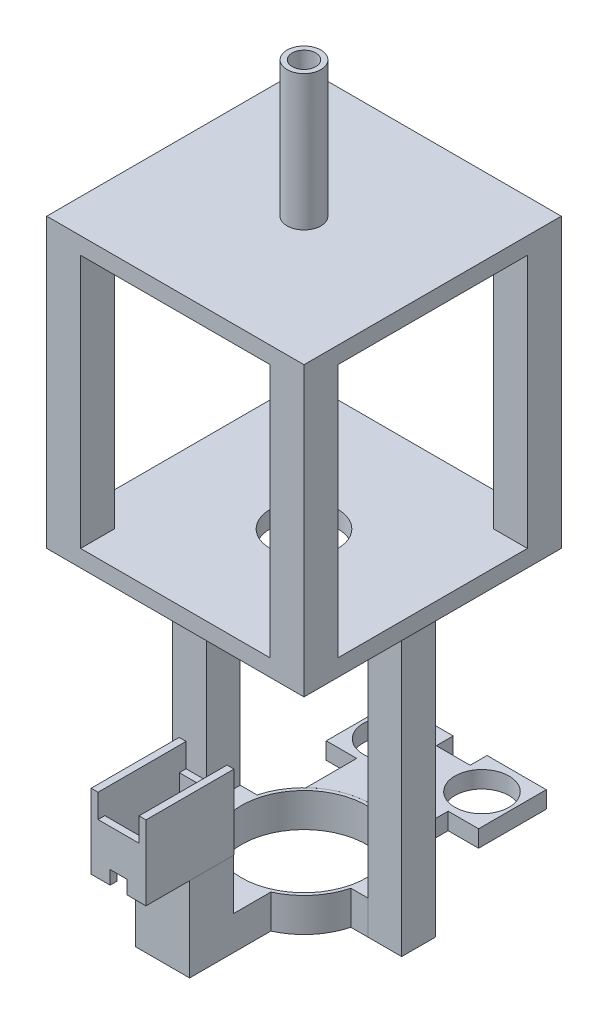
SolidWorks part; units mm, degrees
ref_plane "Front Plane" through (0, 0, 0) normal (0, 0, 1) x (1, 0, 0)
ref_plane "Top Plane" through (0, 0, 0) normal (0, 1, 0) x (1, 0, 0)
ref_plane "Right Plane" through (0, 0, 0) normal (1, 0, 0) x (0, 0, -1)
sketch "Sketch2" plane through (0, 0, 0) normal (0, 1, 0) x (1, 0, 0)
  line L0 (0, 18.5) -> (0, -18.5) construction
  line L1 (-18.5, 0) -> (18.5, 0) construction
  line L2 (0, -5) -> (0, 5) construction
  line L3 (-18.8481, 5) -> (-33.8481, 5)
  line L4 (-33.8481, 5) -> (-33.8481, -5)
  line L5 (-33.8481, -5) -> (-18.8481, -5)
  line L6 (33.8481, -5) -> (18.8481, -5)
  line L7 (33.8481, 5) -> (33.8481, -5)
  line L8 (18.8481, 5) -> (33.8481, 5)
  line L9 (0, 29.0712) -> (22.5, 29.0712)
  line L10 (22.5, 29.0712) -> (22.5, 49.0712)
  line L11 (22.5, 49.0712) -> (5, 49.0712)
  line L12 (-22.5, 49.0712) -> (-22.5, 29.0712)
  line L13 (-22.5, 29.0712) -> (0, 29.0712)
  line L14 (22.5, 39.0712) -> (21.5, 39.0712) construction
  line L20 (-5, 49.0712) -> (-22.5, 49.0712)
  line L21 (0, 44.0712) -> (0, 29.0712) construction
  line L22 (-5, 49.0712) -> (-5, 44.0712)
  line L23 (-5, 44.0712) -> (5, 44.0712)
  line L24 (5, 44.0712) -> (5, 49.0712)
  line L25 (13.5, 47.0712) -> (13.5, 49.0712) construction
  line L26 (13.5, 31.0712) -> (13.5, 29.0712) construction
  line L27 (-13.5, 39.0712) -> (13.5, 39.0712) construction
  line L28 (-13.5, 14.0712) -> (-13.5, 29.0712)
  line L29 (13.5, 29.0712) -> (13.5, 14.0712)
  line L30 (-8, -19.5) -> (8, -19.5) construction
  line L31 (-8, -17.7834) -> (-8, -41.7834)
  line L32 (-8, -41.7834) -> (8, -41.7834)
  line L33 (8, -41.7834) -> (8, -17.7834)
  line L34 (-18.8481, 5) -> (-23.8481, 5) construction
  line L35 (-5.5, -19.5) -> (5.5, -19.5) construction
  line L36 (-23.8481, 5) -> (-23.8481, -5)
  line L37 (23.8481, 5) -> (23.8481, -5)
  circle A0 centre (0, 0) radius 18.5
  circle A1 centre (0, 0) radius 19.5
  circle A2 centre (13.5, 39.0712) radius 8
  circle A3 centre (-13.5, 39.0712) radius 8
  point P9 (0, 0)
  point P45 (0, -19.5)
  point P54 (0, -19.5)
  dimension "D1" = 37
  dimension "D2" = 5
  dimension "D4" = 39
  dimension "D8" = 1
  dimension "D9" = 16
  dimension "D3" = 10
  dimension "D5" = 5
  dimension "D6" = 20
  dimension "D7" = 45
  dimension "D10" = 17.5
  dimension "D11" = 15
  dimension "D12" = 27
  dimension "D13" = 15
  dimension "D14" = 16
  dimension "D15" = 24
  dimension "D16" = 5
extrude "Connector sleeve" add sketch "Sketch2" along normal blind 5 and the other way blind 5 contours A1 A0 | A1 A0 | A1 A0 | A1 A0 region at (-16.3228, 0, -9.6234)
ref_plane "Plane2" through (0, 30, 0) normal (0, 1, 0) x (1, 0, 0)
extrude "Sensor holder" add sketch "Sketch2<10>" along normal blind 5 separate body contours L24 L23 L22 L20 L12 L13 L9 L10 L11 A2 A3 | A1 L29 L9 L13 L28 region at (0, 0, -23.3278) region at (0, 0, -38.234)
sketch "Sketch2<10>" plane through (0, 0, 0) normal (0, 1, 0) x (1, 0, 0) same geometry as "Sketch2"
extrude "Arms" add sketch "Sketch2<18>" along normal blind 85 from offset 5 contours L36 L3 L4 L5 | L8 L37 L6 L7 region at (-28.8481, 0, 0) region at (28.8481, 0, 0) offset against normal yes
sketch "Sketch2<18>" plane through (0, 0, 0) normal (0, 1, 0) x (1, 0, 0) same geometry as "Sketch2"
extrude "Arms2" add sketch "Sketch2<22>" along normal blind 10 from offset 5 contours A1 L3 L4 L5 | A1 L6 L7 L8 | A1 L3 L36 L5 | A1 L6 L37 L8 region at (-21.562, 0, 0) region at (-28.8481, 0, 0) region at (21.562, 0, 0) region at (28.8481, 0, 0) offset against normal yes
sketch "Sketch2<22>" plane through (0, 0, 0) normal (0, 1, 0) x (1, 0, 0) same geometry as "Sketch2"
extrude "Servoholder" add sketch "Sketch2<21>" along normal blind 10 from offset 5 contours A1 L31 L32 L33 region at (0, 0, 30.3552) offset against normal yes
sketch "Sketch2<21>" plane through (0, 0, 0) normal (0, 1, 0) x (1, 0, 0) same geometry as "Sketch2"
sketch "Sketch31" plane through (0, 5, 0) normal (0, 1, 0) x (1, 0, 0)
  line L0 (-8, -41.7834) -> (-8, -28.7834)
  line L1 (-8, -17.7834) -> (-8, -41.7834) construction
  line L2 (-8, -28.7834) -> (8, -28.7834)
  line L3 (8, -41.7834) -> (8, -17.7834) construction
  line L4 (8, -28.7834) -> (8, -41.7834)
  line L5 (8, -41.7834) -> (-8, -41.7834)
  dimension "D1" = 13
extrude "Servoholder2" add sketch "Sketch31" along normal blind 15
sketch "Sketch33" plane through (0, 20, 0) normal (0, 1, 0) x (1, 0, 0)
  line L0 (0, -28.7834) -> (0, -30.7834) construction
  line L1 (8, -28.7834) -> (-8, -28.7834) construction
  line L2 (-8, -41.7834) -> (8, -41.7834) construction
  line L4 (8, -28.7834) -> (-8, -28.7834) construction
  line L6 (-8.1, -28.7834) -> (-8.1, -54.7834)
  line L7 (-8.1, -54.7834) -> (8.1, -54.7834)
  line L8 (8.1, -54.7834) -> (8.1, -28.7834)
  line L9 (0, -41.7834) -> (6.05, -41.7834) construction
  line L10 (0, -54.7834) -> (0, -52.7834) construction
  line L11 (-6.05, -52.7834) -> (6.05, -52.7834)
  line L12 (6.05, -52.7834) -> (6.05, -30.7834)
  line L13 (6.05, -30.7834) -> (-6.05, -30.7834)
  line L14 (-6.05, -52.7834) -> (-6.05, -30.7834)
  line L15 (-8.1, -28.7834) -> (8.1, -28.7834)
  dimension "D1" = 8.1
  dimension "D2" = 26
  dimension "D3" = 6.05
  dimension "D4" = 2
  dimension "D5" = 2
extrude "Servoholder3" add sketch "Sketch33" along normal blind 22
sketch "Servoholder4" plane through (0, 42, 0) normal (0, 1, 0) x (1, 0, 0)
  line L0 (-6.05, -30.7834) -> (-6.05, -28.7834)
  line L1 (8, -28.7834) -> (-8, -28.7834) construction
  line L2 (-6.05, -28.7834) -> (6.05, -28.7834)
  line L3 (8.1, -28.7834) -> (-8.1, -28.7834) construction
  line L4 (6.05, -28.7834) -> (6.05, -30.7834)
  line L5 (6.05, -30.7834) -> (-6.05, -30.7834)
  line L6 (-6.05, -41.7834) -> (6.05, -41.7834) construction
  line L7 (-6.05, -30.7834) -> (-6.05, -52.7834) construction
  line L8 (6.05, -52.7834) -> (6.05, -30.7834) construction
  line L9 (6.05, -54.7834) -> (6.05, -52.7834)
  line L10 (-6.05, -52.7834) -> (-6.05, -54.7834)
  line L11 (-6.05, -54.7834) -> (6.05, -54.7834)
  line L12 (6.05, -52.7834) -> (-6.05, -52.7834)
extrude "Servogrooves" cut sketch "Servoholder4" against normal blind 7
sketch "Sketch36" plane through (0, 0, 54.7834) normal (0, 0, 1) x (1, 0, 0)
  line L0 (0, 20) -> (0, 24) construction
  line L1 (-8.1, 20) -> (8.1, 20) construction
  line L2 (-2.5, 24) -> (2.5, 24)
  line L3 (-2.5, 24) -> (-2.5, 20)
  line L4 (-6.05, 20) -> (6.05, 20) construction
  line L5 (2.5, 24) -> (2.5, 20)
  line L6 (2.5, 20) -> (-2.5, 20)
  point P8 (0, 24)
  dimension "D1" = 4
  dimension "D2" = 2.5
extrude "Servowiring" cut sketch "Sketch36" against normal blind 2
sketch "Sketch4" plane through (0, 80, 0) normal (0, 1, 0) x (1, 0, 0)
  line L1 (-38, -38) -> (38, -38)
  line L2 (-38, -38) -> (-38, 38)
  line L3 (-38, 38) -> (38, 38)
  line L4 (38, -38) -> (38, 38)
  line L5 (-38, -38) -> (38, 38) construction
  line L6 (-38, 38) -> (38, -38) construction
  circle A0 centre (0, 0) radius 10
  point P0 (0, 0)
  dimension "D2" = 20
  dimension "D1" = 76
extrude "Motor enclosure" add sketch "Sketch4" along normal blind 5
sketch "Sketch6" plane through (0, 85, 0) normal (0, 1, 0) x (1, 0, 0)
  line L0 (-38, 38) -> (-28, 38)
  line L1 (38, 38) -> (-38, 38) construction
  line L2 (-28, 38) -> (-28, 28)
  line L3 (-28, 28) -> (-38, 28)
  line L4 (-38, 38) -> (-38, -38) construction
  line L5 (-38, 28) -> (-38, 38)
  line L6 (0, 38) -> (0, -38) construction
  line L7 (-38, -38) -> (38, -38) construction
  line L8 (-38, 0) -> (38, 0) construction
  line L9 (38, -38) -> (38, 38) construction
  line L10 (28, 28) -> (38, 28)
  line L11 (38, 28) -> (38, 38)
  line L12 (38, 38) -> (28, 38)
  line L13 (28, 38) -> (28, 28)
  line L14 (28, -28) -> (38, -28)
  line L15 (38, -28) -> (38, -38)
  line L16 (38, -38) -> (28, -38)
  line L17 (28, -38) -> (28, -28)
  line L18 (-28, -28) -> (-38, -28)
  line L19 (-28, -38) -> (-28, -28)
  line L20 (-38, -28) -> (-38, -38)
  line L21 (-38, -38) -> (-28, -38)
  dimension "D2" = 10
extrude "Motor enclosure 2" add sketch "Sketch6" along normal blind 75
sketch "Sketch7" plane through (0, 160, 0) normal (0, 1, 0) x (1, 0, 0)
  line L0 (-38, 38) -> (38, 38)
  line L1 (38, 38) -> (38, -38)
  line L2 (38, -38) -> (-38, -38)
  line L3 (-38, -28) -> (-38, -38) construction
  line L4 (-38, -38) -> (-38, 38)
extrude "Motor enclosure 3" add sketch "Sketch7" along normal blind 5 contours L1 L2 L4 L0
sketch "Sketch8" plane through (0, 165, 0) normal (0, 1, 0) x (1, 0, 0)
  circle A0 centre (0, 0) radius 5
  point P0 (0, 0)
  dimension "D1" = 10
extrude "Connector" add sketch "Sketch8" along normal blind 40
sketch "Sketch26" plane through (0, 205, 0) normal (0, 1, 0) x (1, 0, 0)
  circle A0 centre (0, 0) radius 3.5
  dimension "D1" = 7
extrude "Cut-Extrude1" cut sketch "Sketch26" against normal up to next (45 mm away)
